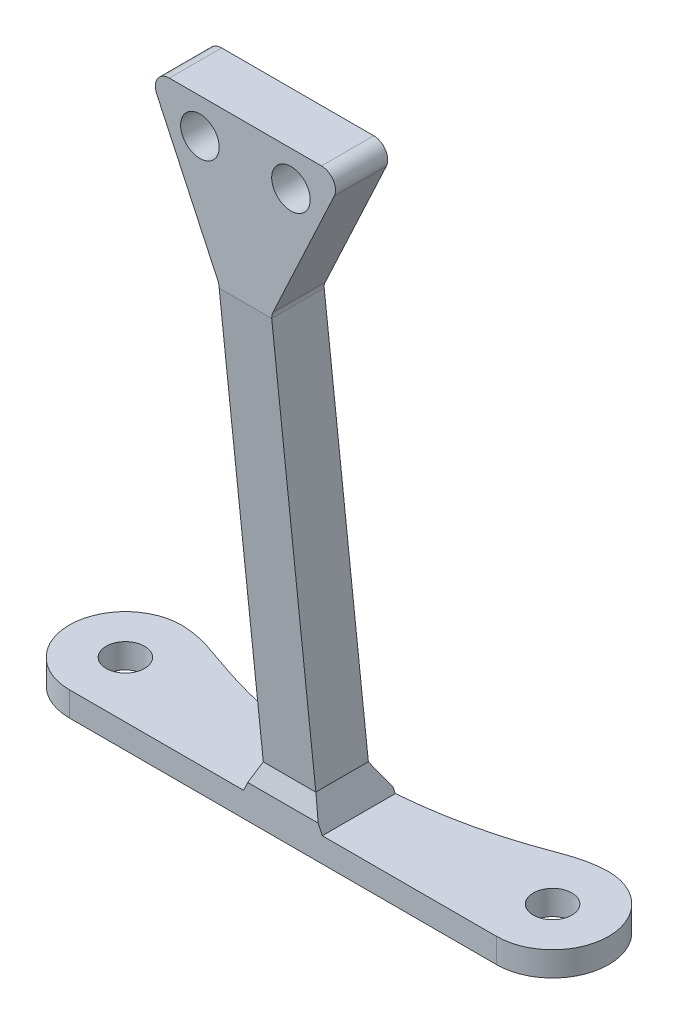
SolidWorks part; units mm, degrees
material "CARBON FIBER TEST"
ref_plane "Front Plane" through (0, 0, 0) normal (0, 0, 1) x (1, 0, 0)
ref_plane "Top Plane" through (0, 0, 0) normal (0, 1, 0) x (1, 0, 0)
ref_plane "Right Plane" through (0, 0, 0) normal (1, 0, 0) x (0, 0, -1)
sketch "Sketch1" plane through (0, 0, 0) normal (0, 1, 0) x (1, 0, 0)
  line L0 (0, 0) -> (30.5, 0) construction
  line L1 (15.25, 0) -> (15.25, 7.3605) construction
  dimension "D1" = 30.5
sketch "Sketch2" plane through (0, 0, 0) normal (0, 1, 0) x (1, 0, 0)
  line L0 (0, 0) -> (30.5, 0) construction
  line L1 (0, 4) -> (30.5, 4)
  line L2 (0, -4) -> (30.5, -4)
  circle A0 centre (0, 0) radius 1.375
  circle A1 centre (30.5, 0) radius 1.375
  arc A2 (0, 4) -> (0, -4) centre (0, 0) ccw
  arc A3 (30.5, -4) -> (30.5, 4) centre (30.5, 0) ccw
  point P6 (15.25, 0)
  dimension "D1" = 2.75
  dimension "D2" = 2.75
  dimension "D3" = 4
extrude "Boss-Extrude1" add sketch "Sketch2" along normal blind 1.75
sketch "Sketch3" plane through (0, 1.75, 0) normal (0, 1, 0) x (1, 0, 0)
  line L2 (0, -4) -> (30.5, -4)
  line L3 (30.5, 4) -> (0, 4)
  line L4 (0, -4) -> (30.5, -4) construction
  line L5 (30.5, 4) -> (0, 4)
  arc A2 (0, 4) -> (0, -4) centre (0, 0) ccw
  arc A3 (30.5, -4) -> (30.5, 4) centre (30.5, 0) ccw
  arc A4 (0, 4) -> (0, -4) centre (0, 0) ccw construction
  arc A5 (30.5, -4) -> (30.5, 4) centre (30.5, 0) ccw construction
  spline S0 degree 3 poles (0, 4) (1.4051, 4) (4.6252, 2.6454) (11.3629, 0.967) (19.1117, 0.967) (25.9293, 2.6454) (29.0155, 4) (30.5, 4) knots 0 0 0 0 0.13251 0.331274 0.668726 0.86749 1 1 1 1
  dimension "D2" = 4
  dimension "D3" = 3
  dimension "D4" = 4
  dimension "D5" = 10
  dimension "D6" = 10
  dimension "D7" = 1.5
  dimension "D1" = 0
extrude "Cut-Extrude1" cut sketch "Sketch3" against normal blind 10
sketch "Sketch4" plane through (0, 1.75, 0) normal (0, -1, 0) x (1, 0, 0)
  line L0 (15.25, -1.1003) -> (21.3646, -1.1003) construction
  line L1 (13.375, -0.4251) -> (17.125, -0.4251)
  line L2 (13.375, -0.4251) -> (13.375, 3.3249)
  line L3 (13.375, 3.3249) -> (17.125, 3.3249)
  line L4 (17.125, -0.4251) -> (17.125, 3.3249)
  line L5 (13.375, -0.4251) -> (17.125, 3.3249) construction
  line L6 (13.375, 3.3249) -> (17.125, -0.4251) construction
  line L7 (15.25, 0) -> (15.25, -7.3605) construction
  line L10 (15.25, 1.4499) -> (16.1951, 1.4499) construction
  line L11 (0, 4) -> (30.5, 4) construction
  spline S1 degree 3 poles (0, -4) (1.4051, -4) (4.6252, -2.6454) (11.3629, -0.967) (19.1117, -0.967) (25.9293, -2.6454) (29.0155, -4) (30.5, -4) knots 0 0 0 0 0.13251 0.331274 0.668726 0.86749 1 1 1 1 construction
  point P0 (15.25, 1.4499)
  point P5 (15.25, 4)
  dimension "D1" = 3.75
ref_plane "Plane1" through (0, 45.81, 0) normal (0, 1, 0) x (1, 0, 0)
sketch "Sketch5" plane through (0, 45.81, 0) normal (0, 1, 0) x (1, 0, 0)
  line L0 (13.375, 0.4251) -> (13.375, -3.3249) construction
  line L1 (13.375, -7.8249) -> (17.125, -7.8249)
  line L2 (13.375, -7.8249) -> (13.375, -4.0749)
  line L3 (13.375, -4.0749) -> (17.125, -4.0749)
  line L4 (17.125, -7.8249) -> (17.125, -4.0749)
  line L5 (13.375, -7.8249) -> (17.125, -4.0749) construction
  line L6 (13.375, -4.0749) -> (17.125, -7.8249) construction
  line L9 (13.375, 0.4251) -> (17.125, 0.4251) construction
  point P0 (15.25, -5.9499)
  dimension "D1" = 4.5
loft "Loft1" add profiles "Sketch5", "Sketch4"
chamfer "Chamfer1" distance 2 angle 25 4 edges
sketch "Sketch6" plane through (0, 14.1813, 0) normal (0, 0, 1) x (-1, 0, 0)
  line L0 (-22.25, -31.6287) -> (-8.25, -31.6287)
  line L1 (-17.125, -31.6287) -> (-13.375, -31.6287) construction
  line L2 (-8.25, -31.6287) -> (-15.25, -16.6287)
  line L3 (-15.25, -16.6287) -> (-22.25, -31.6287)
  line L4 (-15.25, -31.6287) -> (-15.25, 49.6908) construction
  line L5 (-13.375, -31.6287) -> (-17.125, -31.6287) construction
  point P5 (-15.25, -31.6287)
  dimension "D1" = 7
  dimension "D2" = 15
extrude "Boss-Extrude2" add sketch "Sketch6" along normal up to surface (4.8749 mm away) from offset 2.95
fillet "Fillet1" radius 1 4 edges at (8.25, 45.81, 5.3874) (13.375, 34.8279, 4.8282) (17.125, 34.8279, 4.8282) (22.25, 45.81, 5.3874)
sketch "Sketch8" plane through (0, 0, 0) normal (0, 0, 1) x (1, 0, 0)
  line L0 (15.25, 46.5064) -> (15.25, 39.1113) construction
  line L1 (9.8202, 45.81) -> (20.6798, 45.81) construction
  circle A0 centre (12, 43.31) radius 1.375
  circle A1 centre (18.5, 43.31) radius 1.375
  dimension "D1" = 2.75
  dimension "D2" = 3.25
  dimension "D3" = 3.25
  dimension "D4" = 2.5
extrude "Cut-Extrude2" cut sketch "Sketch8" along normal through all
ref_plane "Plane2" through (0, 0, 6.6806) normal (0, 0, 1) x (1, 0, 0)
sketch "Sketch9" plane through (0, 0, 6.6806) normal (0, 0, 1) x (1, 0, 0)
  line L0 (13.2812, 35.0289) -> (8.914, 44.3871) construction
  line L1 (9.8202, 45.81) -> (20.6798, 45.81) construction
  line L2 (21.586, 44.3871) -> (17.2188, 35.0289) construction
  line L3 (13.2812, 35.0289) -> (8.914, 44.3871)
  line L4 (9.8202, 45.81) -> (20.6798, 45.81)
  line L5 (21.586, 44.3871) -> (17.2188, 35.0289)
  line L6 (13.375, 34.606) -> (17.125, 34.606)
  arc A0 (9.8202, 45.81) -> (8.914, 44.3871) centre (9.8202, 44.81) ccw construction
  arc A1 (21.586, 44.3871) -> (20.6798, 45.81) centre (20.6798, 44.81) ccw construction
  arc A2 (9.8202, 45.81) -> (8.914, 44.3871) centre (9.8202, 44.81) ccw
  arc A3 (21.586, 44.3871) -> (20.6798, 45.81) centre (20.6798, 44.81) ccw
  arc A4 (17.2188, 35.0289) -> (17.125, 34.606) centre (18.125, 34.606) ccw construction
  arc A5 (13.375, 34.606) -> (13.2812, 35.0289) centre (12.375, 34.606) ccw construction
  arc A6 (17.2188, 35.0289) -> (17.125, 34.606) centre (18.125, 34.606) ccw
  arc A7 (13.375, 34.606) -> (13.2812, 35.0289) centre (12.375, 34.606) ccw
extrude "Cut-Extrude4" cut sketch "Sketch9" along normal through all
